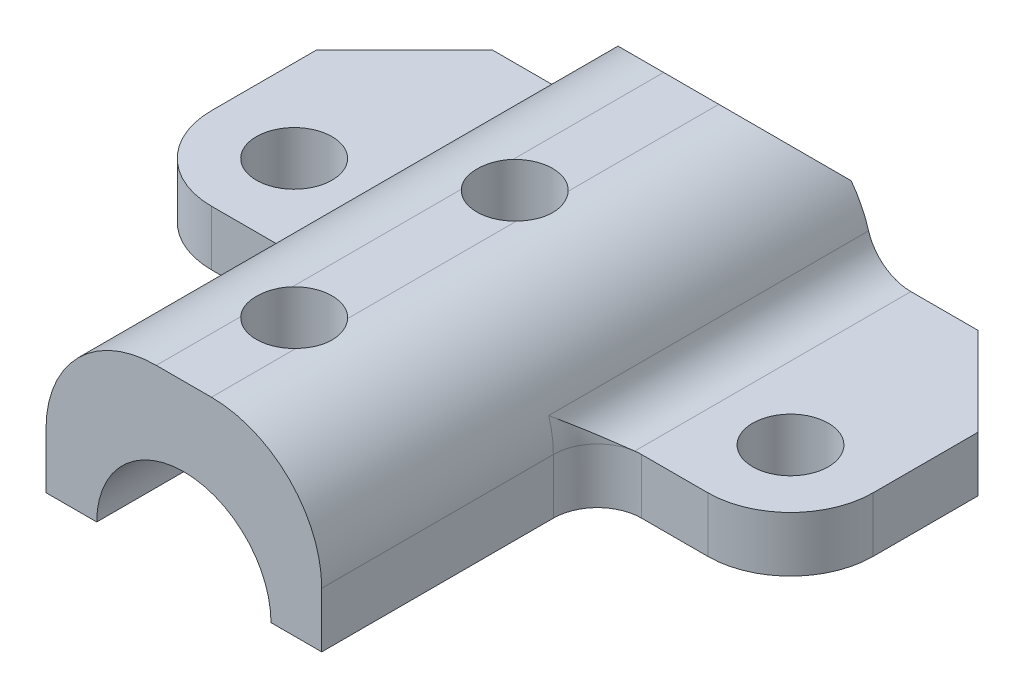
SolidWorks part; units mm, degrees
ref_plane "Front Plane" through (0, 0, 0) normal (0, 0, 1) x (1, 0, 0)
ref_plane "Top Plane" through (0, 0, 0) normal (0, 1, 0) x (1, 0, 0)
ref_plane "Right Plane" through (0, 0, 0) normal (1, 0, 0) x (0, 0, -1)
sketch "Sketch1" plane through (0, 0, 0) normal (0, 1, 0) x (1, 0, 0)
  line L1 (-6.25, -6.25) -> (6.25, -6.25)
  line L2 (-6.25, -6.25) -> (-6.25, 6.25)
  line L3 (-6.25, 6.25) -> (6.25, 6.25)
  line L4 (6.25, -6.25) -> (6.25, 6.25)
  line L5 (-6.25, -6.25) -> (6.25, 6.25) construction
  line L6 (-6.25, 6.25) -> (6.25, -6.25) construction
  line L7 (-15, 6.25) -> (15, 6.25)
  line L8 (-15, 6.25) -> (-15, 18.75)
  line L9 (-15, 18.75) -> (15, 18.75)
  line L10 (15, 6.25) -> (15, 18.75)
  line L11 (-15, 6.25) -> (15, 18.75) construction
  line L12 (-15, 18.75) -> (15, 6.25) construction
  point P0 (0, 0)
  point P6 (0, 12.5)
  dimension "D1" = 30
  dimension "D2" = 25
  dimension "D3" = 12.5
  dimension "D4" = 12.5
extrude "Boss-Extrude1" add sketch "Sketch1" along normal blind 7.5 contours L7 L10 L9 L8 L3 | L1 L4 L3 L2 region at (0, 0, 0) region at (0, 0, -12.5)
sketch "Sketch2" plane through (0, 0, -6.25) normal (0, 0, 1) x (1, 0, 0)
  line L0 (-6.25, 7.5) -> (-6.25, 0) construction
  line L1 (-15, 7.5) -> (-6.25, 7.5)
  line L2 (-15, 7.5) -> (-15, 2.5)
  line L3 (-15, 2.5) -> (-6.25, 2.5)
  line L4 (-6.25, 7.5) -> (-6.25, 2.5)
  line L5 (6.25, 7.5) -> (6.25, 0) construction
  line L6 (15, 7.5) -> (6.25, 7.5)
  line L7 (15, 7.5) -> (15, 2.5)
  line L8 (15, 2.5) -> (6.25, 2.5)
  line L9 (6.25, 7.5) -> (6.25, 2.5)
  line L10 (-15, 0) -> (-6.25, 0) construction
  dimension "D1" = 2.5
extrude "Cut-Extrude1" cut sketch "Sketch2" against normal through all
sketch "Sketch3" plane through (0, 0, 6.25) normal (0, 0, 1) x (1, 0, 0)
  circle A0 centre (0, 0) radius 3.95
  dimension "D1" = 7.9
extrude "Cut-Extrude2" cut sketch "Sketch3" against normal blind 20
chamfer "Chamfer1" distance 4 angle 45 2 edges at (15, 1.25, -18.75) (-15, 1.25, -18.75)
fillet "Fillet1" radius 3.75 2 edges at (-15, 1.25, -6.25) (15, 1.25, -6.25)
fillet "Fillet2" radius 5 2 edges at (-6.25, 7.5, -6.25) (6.25, 7.5, -6.25)
fillet "Fillet3" radius 2 2 edges at (-6.25, 2.5, -12.5) (6.25, 2.5, -12.5)
sketch "Sketch4" plane through (0, 2.5, 0) normal (0, 1, 0) x (1, 0, 0)
  circle A0 centre (-11.25, 10) radius 1.7145
  circle A1 centre (11.25, 10) radius 1.7145
  arc A2 (-15, 10) -> (-11.25, 6.25) centre (-11.25, 10) ccw construction
  arc A3 (11.25, 6.25) -> (15, 10) centre (11.25, 10) ccw construction
  dimension "D1" = 3.429
extrude "Cut-Extrude3" cut sketch "Sketch4" against normal through all
sketch "Sketch5" plane through (0, 7.5, 0) normal (0, 1, 0) x (1, 0, 0)
  line L0 (-1.25, -6.25) -> (1.25, -6.25) construction
  line L1 (0, 0) -> (0, 2.194) construction
  circle A0 centre (0, 8.75) radius 1.7145
  circle A1 centre (0, -1.25) radius 1.7145
  dimension "D3" = 3.429
  dimension "D1" = 10
  dimension "D2" = 5
extrude "Cut-Extrude4" cut sketch "Sketch5" against normal through all
fillet "Fillet4" radius 2 4 edges at (6.1976, 3.2218, -6.25) (-6.1976, 3.2218, -6.25) (6.25, 1.25, -6.25) (-6.25, 1.25, -6.25)
chamfer "Chamfer3" distance 2 angle 45 1 edges at (0, 7.5, -18.75) tangent propagation no
